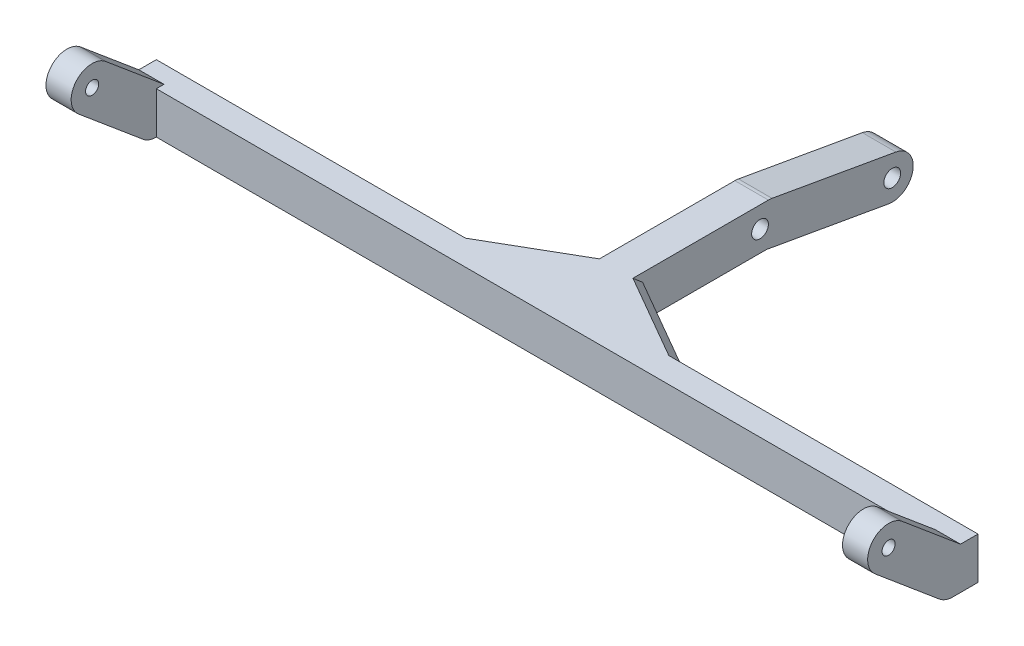
SolidWorks part; units mm, degrees
material "1060 合金"
ref_plane "前视基准面" through (0, 0, 0) normal (0, 0, 1) x (1, 0, 0)
ref_plane "上视基准面" through (0, 0, 0) normal (0, 1, 0) x (1, 0, 0)
ref_plane "右视基准面" through (0, 0, 0) normal (1, 0, 0) x (0, 0, -1)
sketch "草图1" plane through (0, 0, 0) normal (0, 1, 0) x (1, 0, 0)
  line L0 (0, 105.6524) -> (0, -42.1429) construction
  line L1 (98, 0) -> (-98, 0)
  line L7 (-24.7846, 8) -> (-4, 20)
  line L10 (-98, 8) -> (-24.7846, 8)
  line L20 (4, 55) -> (-4, 55)
  line L24 (-4, 20) -> (-4, 55)
  line L25 (-98, 0) -> (-98, 8)
  line L28 (98, 0) -> (98, 8)
  line L29 (4, 20) -> (4, 55)
  line L32 (98, 8) -> (24.7846, 8)
  line L33 (24.7846, 8) -> (4, 20)
  point P17 (0, -11.5)
  point P18 (0, 11.5)
  point P19 (0, 17.5)
  point P24 (0, -25)
  point P34 (0, 55)
  point P37 (0, 0)
  dimension "D1" = 8
  dimension "D2" = 4
  dimension "D3" = 30
  dimension "D4" = 55
  dimension "D7" = 12
  dimension "D9" = 98
extrude "凸台-拉伸1" add sketch "草图1" along normal mid plane 10
fillet "圆角1" radius 5 2 edges at (0, -5, -55) (0, 5, -55)
sketch "草图9" plane through (0, 0, 0) normal (1, 0, 0) x (0, 0, -1)
  line L0 (3.2139, 3.8302) -> (-12.107, 16.686)
  line L1 (-3.2139, -3.8302) -> (-18.5348, 9.0255)
  line L2 (0, -5) -> (8, -5) construction
  arc A0 (-3.2139, -3.8302) -> (3.2139, 3.8302) centre (0, 0) ccw
  arc A1 (-12.107, 16.686) -> (-18.5348, 9.0255) centre (-15.3209, 12.8558) ccw
  circle A2 centre (-15.3209, 12.8558) radius 1.5636
  dimension "D1" = 40
  dimension "D2" = 20
extrude "凸台-拉伸4" add sketch "草图9" against normal blind 6 from surface starting at face at (98, 0, -4)
extrude "凸台-拉伸5" add sketch "草图9<2>" along normal blind 6 from surface starting at face at (-98, 0, -4)
sketch "草图9<2>" plane through (0, 0, 0) normal (1, 0, 0) x (0, 0, -1) same geometry as "草图9"
sketch "草图10" plane through (0, 0, 0) normal (1, 0, 0) x (0, 0, -1)
  line L0 (50.8682, 4.924) -> (80.4125, -0.2854)
  line L1 (49.1318, -4.924) -> (78.676, -10.1335)
  line L2 (20, -5) -> (50, -5) construction
  arc A0 (50.8682, 4.924) -> (49.1318, -4.924) centre (50, 0) ccw
  arc A1 (78.676, -10.1335) -> (80.4125, -0.2854) centre (79.5442, -5.2094) ccw
  circle A2 centre (79.5442, -5.2094) radius 2
  arc A3 (50, -5) -> (55, 0) centre (50, 0) ccw construction
  dimension "D3" = 4
  dimension "D1" = 10
  dimension "D2" = 30
extrude "凸台-拉伸6" add sketch "草图10" along normal mid plane 8
sketch "草图11" plane through (0, 0, 0) normal (1, 0, 0) x (0, 0, -1)
  circle A0 centre (48, 0) radius 2
  dimension "D1" = 4
  dimension "D2" = 48
extrude "切除-拉伸1" cut sketch "草图11" against normal through all both and the other way through all
chamfer "倒角1" distance 2 angle 45 10 edges at (61.3923, -5, -8) (98, 0, -8) (61.3923, 5, -8) (-61.3923, -5, -8) (-98, 0, -8) (-61.3923, 5, -8) (14.3923, -5, -14) (14.3923, 5, -14) (-14.3923, -5, -14) (-14.3923, 5, -14)
